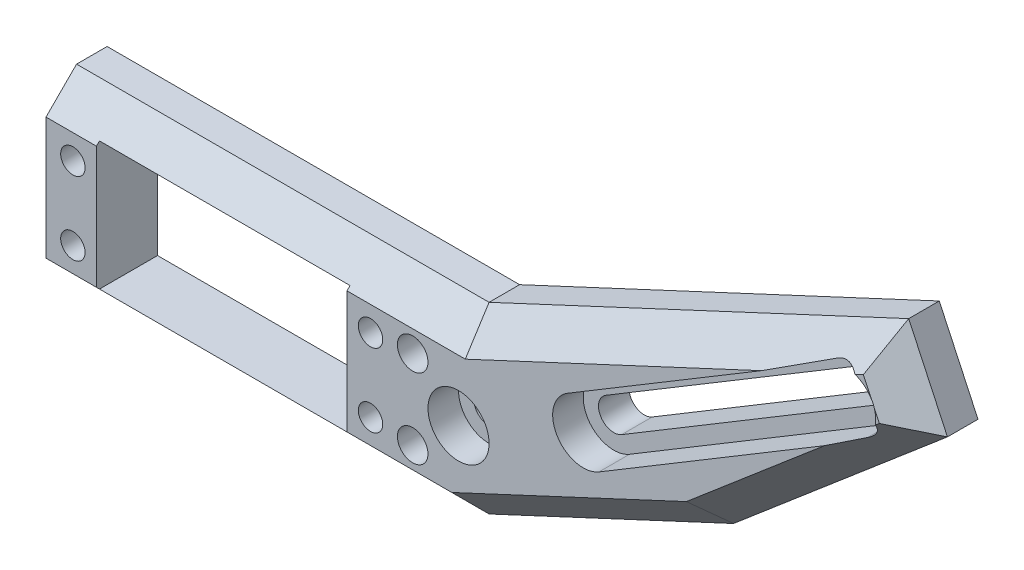
SolidWorks part; units mm, degrees
ref_plane "前视基准面" through (0, 0, 0) normal (0, 0, 1) x (1, 0, 0)
ref_plane "上视基准面" through (0, 0, 0) normal (0, 1, 0) x (1, 0, 0)
ref_plane "右视基准面" through (0, 0, 0) normal (1, 0, 0) x (0, 0, -1)
other "Configuration Table"
sketch "Sketch1" plane through (0, 0, 0) normal (0, 0, 1) x (1, 0, 0)
  line L1 (-28.75, -15) -> (28.75, -15)
  line L2 (-28.75, -15) -> (-28.75, 15)
  line L3 (-28.75, 15) -> (28.75, 15)
  line L4 (28.75, -15) -> (28.75, 15)
  line L5 (-28.75, -15) -> (28.75, 15) construction
  line L6 (-28.75, 15) -> (28.75, -15) construction
  point P0 (0, 0)
  dimension "D1" = 57.5
  dimension "D2" = 30
extrude "Boss-Extrude1" add sketch "Sketch1" along normal blind 30
sketch "Sketch2" plane through (0, 0, 30) normal (0, 0, 1) x (1, 0, 0)
  line L1 (-20.5, -10.5) -> (20.5, -10.5)
  line L2 (-20.5, -10.5) -> (-20.5, 10.5)
  line L3 (-20.5, 10.5) -> (20.5, 10.5)
  line L4 (20.5, -10.5) -> (20.5, 10.5)
  line L5 (-20.5, -10.5) -> (20.5, 10.5) construction
  line L6 (-20.5, 10.5) -> (20.5, -10.5) construction
  point P0 (0, 0)
  dimension "D1" = 41
  dimension "D2" = 21
extrude "Cut-Extrude1" cut sketch "Sketch2" against normal blind 25
ref_plane "Plane1" through (0, 0, 15) normal (0, 0, 1) x (1, 0, 0)
sketch "Sketch8" plane through (0, 0, 30) normal (0, 0, 1) x (1, 0, 0)
  line L0 (0, 0) -> (24.35, 0) construction
  line L1 (24.35, 0) -> (24.35, 6) construction
  line L2 (0, 0) -> (0, 15) construction
  line L3 (28.75, 15) -> (-28.75, 15) construction
  circle A0 centre (24.35, 6) radius 2
  circle A1 centre (24.35, -6) radius 2
  circle A2 centre (-24.35, -6) radius 2
  circle A3 centre (-24.35, 6) radius 2
  dimension "D3" = 4
  dimension "D1" = 6
  dimension "D2" = 24.35
extrude "Cut-Extrude6" cut sketch "Sketch8" against normal blind 10
sketch "Sketch10" plane through (0, 0, 5) normal (0, 0, 1) x (1, 0, 0)
  line L0 (0, 0) -> (-10, 0) construction
  circle A0 centre (-10, 0) radius 5
  dimension "D2" = 10
  dimension "D1" = 10
extrude "Cut-Extrude8" cut sketch "Sketch10" against normal blind 10
sketch "Sketch11" plane through (28.75, 0, 0) normal (1, 0, 0) x (0, 0, -1)
  line L0 (-30, 0) -> (0, 0) construction
  line L1 (-30, -15) -> (-30, 15) construction
  line L2 (0, 0) -> (-15, 0) construction
  line L3 (-15, -15) -> (-15, 15)
  line L4 (-30, 15) -> (0, 15) construction
  line L5 (-15, 15) -> (-11.75, 15)
  line L6 (-11.75, 15) -> (-11.75, 22.5)
  line L7 (-11.75, 22.5) -> (-18.25, 22.5)
  line L8 (-18.25, 22.5) -> (-18.25, 15)
  line L9 (-18.25, 15) -> (-15, 15)
  line L10 (7.5, 3.25) -> (0, 3.25)
  line L11 (0, 3.25) -> (0, 0)
  line L12 (0, -3.25) -> (7.5, -3.25)
  line L13 (0, 0) -> (0, -3.25)
  line L14 (7.5, -3.25) -> (7.5, 3.25)
  line L15 (-11.75, -22.5) -> (-11.75, -15)
  line L16 (-11.75, -15) -> (-15, -15)
  line L17 (-18.25, -15) -> (-18.25, -22.5)
  line L18 (-15, -15) -> (-18.25, -15)
  line L19 (-18.25, -22.5) -> (-11.75, -22.5)
  line L20 (-37.5, -3.25) -> (-30, -3.25)
  line L21 (-30, -3.25) -> (-30, 0)
  line L22 (-30, 3.25) -> (-37.5, 3.25)
  line L23 (-30, 0) -> (-30, 3.25)
  line L24 (-37.5, 3.25) -> (-37.5, -3.25)
  circle A0 centre (-15, 0) radius 7.5 construction
  point P12 (-15, 0)
  point P34 (-15, 0)
  line M5 (0, -15) -> (0, 15)
  line M6 (0, 15) -> (-30, 15)
  line M7 (-30, 15) -> (-30, -15)
  line M8 (-30, -15) -> (0, -15)
  dimension "D1" = 15
  dimension "D2" = 6.5
  dimension "D3" = 7.5
  dimension "D4" = 4
extrude "Boss-Extrude2" [suppressed] add sketch "Sketch11" against normal up to surface (8.25 mm away) contours L22 L24 L20 M7 | L17 L19 L15 M8 | L12 L14 L10 M5 | L7 L8 L6 M6
sketch "Sketch12" plane through (28.75, 0, 0) normal (1, 0, 0) x (0, 0, -1)
  line L20 (-36.5, 15) -> (-30, 15)
  line L21 (-30, -15) -> (-30, -21.5)
  line L22 (0, -15) -> (-11.75, -15)
  line L23 (0, 3.25) -> (0, 15)
  line L40 (0, -15) -> (0, 15)
  line L45 (0, 15) -> (-30, 15)
  line L50 (-30, 15) -> (-30, -15)
  line L55 (-30, -15) -> (0, -15)
  line L60 (0, -15) -> (0, 15)
  line L65 (0, 15) -> (-30, 15)
  line L70 (-30, 15) -> (-30, -15)
  line L75 (-30, -15) -> (0, -15)
  dimension "D1" = 0
extrude "Boss-Extrude3" [suppressed] add sketch "Sketch12" along normal blind 30
sketch "Sketch13" plane through (0, 0, 30) normal (0, 0, 1) x (1, 0, 0)
  line L0 (28.75, 15) -> (38.75, 15)
  line L1 (38.75, 15) -> (107.4107, 47.017)
  line L3 (113.75, 33.4224) -> (78.75, 3.6523)
  line L4 (78.75, 3.6523) -> (38.75, -15)
  line L5 (38.75, -15) -> (28.75, -15)
  line L6 (-28.75, -15) -> (28.75, -15) construction
  line L7 (38.75, 15) -> (38.75, -15) construction
  line L8 (38.75, -15) -> (93.0307, -15) construction
  line L9 (78.75, 3.6523) -> (97.9021, 3.6523) construction
  line L10 (38.75, 15) -> (83.4484, 15) construction
  line L11 (28.75, -15) -> (28.75, 15)
  line L12 (107.4107, 47.017) -> (113.75, 33.4224)
  dimension "D1" = 10
  dimension "D2" = 25
  dimension "D3" = 40
  dimension "D4" = 25
  dimension "D5" = 15
  dimension "D6" = 75
extrude "Boss-Extrude4" add sketch "Sketch13" against normal blind 30
sketch "Sketch16" plane through (1.1757, -2.5212, 0) normal (-0.4226, 0.9063, 0) x (0.9063, 0.4226, 0)
  line L0 (117.2174, -15) -> (97.2174, -15) construction
  line L1 (117.2174, 0) -> (117.2174, -30) construction
  line L2 (-18.5694, -15) -> (18.5694, -15) construction
  line L3 (97.2174, -15) -> (74.7174, -15) construction
  line L4 (67.2174, -15) -> (82.2174, -15) construction
  line L5 (67.2174, -12.5) -> (82.2174, -12.5)
  line L6 (67.2174, -17.5) -> (82.2174, -17.5)
  circle A0 centre (97.2174, -15) radius 5
  arc A1 (67.2174, -12.5) -> (67.2174, -17.5) centre (67.2174, -15) ccw
  arc A2 (82.2174, -17.5) -> (82.2174, -12.5) centre (82.2174, -15) ccw
  point P10 (74.7174, -15)
  dimension "D1" = 10
  dimension "D4" = 2.5
  dimension "D2" = 20
  dimension "D3" = 15
  dimension "D5" = 22.5
extrude "Cut-Extrude10" cut sketch "Sketch16" against normal blind 30
chamfer "Chamfer5" distance 5 angle 45 13 edges at (-28.75, 0, 0) (5, -15, 0) (58.75, -5.6738, 0) (96.25, 18.5374, 0) (110.5804, 40.2197, 0) (73.0804, 31.0085, 0) (5, 15, 0) (5, -15, 30) (58.75, -5.6738, 30) (96.25, 18.5374, 30) (73.0804, 31.0085, 30) (5, 15, 30) (110.5804, 40.2197, 30)
sketch "Sketch19" plane through (0, 0, 30) normal (0, 0, 1) x (1, 0, 0)
  line L0 (38.75, 15) -> (38.75, -15) construction
  line L1 (38.75, -15) -> (38.75, 0) construction
  line L2 (38.75, 0) -> (31.25, 0) construction
  line L3 (31.25, 0) -> (31.25, 6.5) construction
  circle A1 centre (38.75, 0) radius 2.5
  circle A2 centre (31.25, 6.5) radius 2.5
  circle A4 centre (31.25, -6.5) radius 2.5
  point P12 (38.75, 0.1514)
  dimension "D1" = 5
  dimension "D2" = 5
  dimension "D3" = 7.5
  dimension "D4" = 6.5
extrude "Cut-Extrude12" cut sketch "Sketch19" against normal blind 30
sketch "Sketch20" plane through (0, 0, 5) normal (0, 0, 1) x (1, 0, 0)
  circle A0 centre (-10, 0) radius 7.5
  dimension "D1" = 15
extrude "Cut-Extrude13" cut sketch "Sketch20" against normal blind 2.5
sketch "Sketch29" plane through (0, 15, 0) normal (0, 1, 0) x (1, 0, 0)
  line L5 (-28.75, -30) -> (-28.75, -20)
  line L6 (-28.75, -25) -> (-28.75, -5) construction
  line L7 (-28.75, -20) -> (113.75, -20)
  line L8 (113.75, -5) -> (113.75, -25) construction
  line L9 (113.75, -20) -> (113.75, -30)
  line L10 (113.75, -30) -> (-28.75, -30)
  line L11 (-28.75, -20) -> (-28.75, 0)
  line L12 (-28.75, 0) -> (113.75, 0)
  line L13 (113.75, 0) -> (113.75, -20)
  line M5 (38.75, -5) -> (-28.75, -5)
  line M8 (38.75, -25) -> (38.75, -5)
  line M9 (-28.75, -5) -> (-28.75, -25)
  dimension "D1" = 10
extrude "Cut-Extrude15" cut sketch "Sketch29" against normal through all both and the other way through all contours L7 M9 M8 M5 | L13 L12 L11 L7 M5 M8 region at (5, 15, 12.5) region at (63.1633, 15, 8.6224)
sketch "Sketch30" plane through (0, 0, 30) normal (0, 0, 1) x (1, 0, 0)
  line L0 (106.3003, 37.5674) -> (125.3057, 37.5674) construction
  line L1 (0, 0) -> (13.5097, 0) construction
  line L3 (107.6082, 34.7624) -> (104.9923, 40.3724) construction
  line L4 (106.3003, 37.5674) -> (102.0144, 34.9922) construction
  line L6 (59.1561, 9.2403) -> (102.0144, 34.9922) construction
  line L7 (57.8685, 11.3832) -> (100.7268, 37.1351)
  line L8 (60.4437, 7.0974) -> (103.302, 32.8493)
  arc A1 (57.8685, 11.3832) -> (60.4437, 7.0974) centre (59.1561, 9.2403) ccw
  arc A2 (103.302, 32.8493) -> (100.7268, 37.1351) centre (102.0144, 34.9922) ccw
  point P4 (80.5852, 22.1163)
  dimension "D1" = 2.5
  dimension "D2" = 50
  dimension "D3" = 5
  dimension "D4" = 149
extrude "Cut-Extrude16" cut sketch "Sketch30" against normal through all
sketch "Sketch31" plane through (0, 0, 30) normal (0, 0, 1) x (1, 0, 0)
  line L0 (102.0144, 34.9922) -> (59.1561, 9.2403) construction
  line L1 (104.5896, 30.7064) -> (61.7312, 4.9545)
  line L2 (99.4392, 39.2781) -> (56.5809, 13.5262)
  arc A0 (104.5896, 30.7064) -> (99.4392, 39.2781) centre (102.0144, 34.9922) ccw
  arc A1 (56.5809, 13.5262) -> (61.7312, 4.9545) centre (59.1561, 9.2403) ccw
  point P4 (80.5852, 22.1163)
  dimension "D1" = 5
extrude "Cut-Extrude17" cut sketch "Sketch31" against normal blind 5
ref_axis "Axis1" through (38.75, 0, 23.5478) along (0, 0, 1)
sketch "Sketch32" plane through (0, 0, 30) normal (0, 0, 1) x (1, 0, 0)
  circle A0 centre (38.75, 0) radius 5
  dimension "D1" = 10
extrude "Cut-Extrude18" cut sketch "Sketch32" against normal blind 5
sketch "Sketch34" plane through (0, 0, 20) normal (0, 0, -1) x (-1, 0, 0)
  line L0 (-102.0144, 34.9922) -> (-110.5804, 40.2197) construction
  line L1 (-107.4107, 47.017) -> (-113.75, 33.4224) construction
